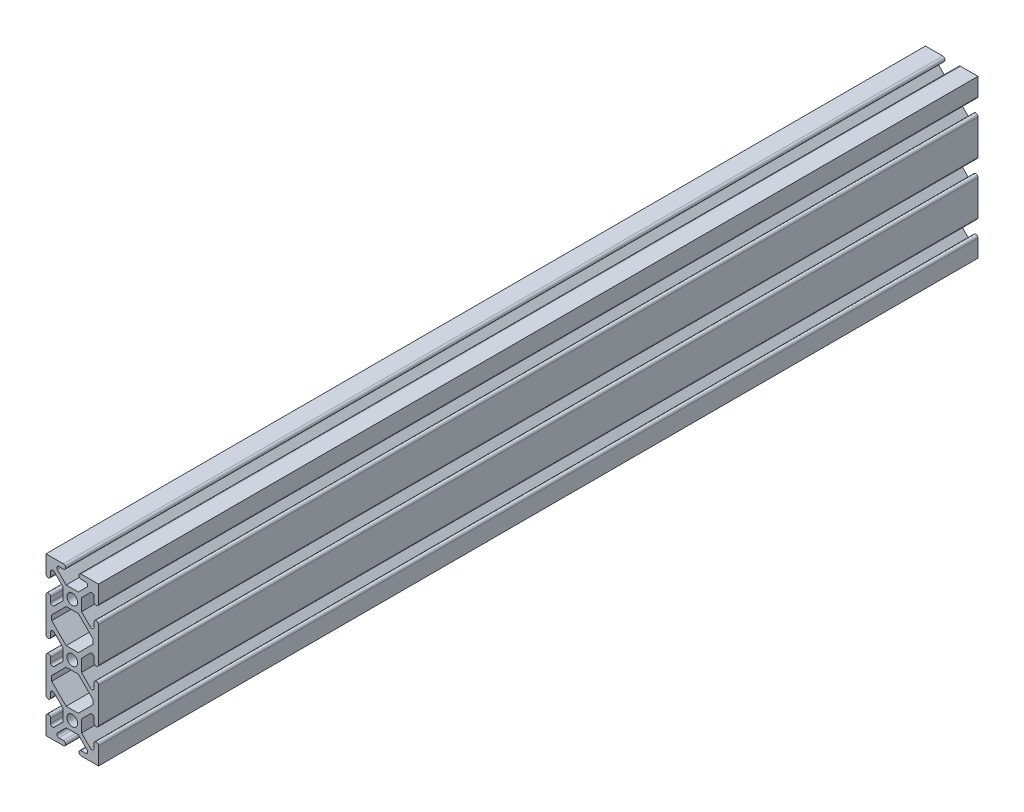
SolidWorks part; units mm, degrees
ref_plane "Front Plane" through (0, 0, 0) normal (0, 0, 1) x (1, 0, 0)
ref_plane "Top Plane" through (0, 0, 0) normal (0, 1, 0) x (1, 0, 0)
ref_plane "Right Plane" through (0, 0, 0) normal (1, 0, 0) x (0, 0, -1)
sketch "Sketch1" plane through (0, 0, 0) normal (0, 0, 1) x (1, 0, 0)
  line L0 (-8.7558, -7.1932) -> (-4.5085, -2.9459)
  line L1 (-9.9314, 13.906) -> (-9.9314, 11.494)
  line L2 (-9.9314, 13.906) -> (-2.9459, 20.8915)
  line L3 (2.9459, 4.5085) -> (9.9314, 11.494)
  line L4 (-4.5085, 2.9459) -> (-4.5085, -2.9459)
  line L5 (-4.5085, 2.9459) -> (-8.7558, 7.1932)
  line L6 (8.7558, 7.1932) -> (4.5085, 2.9459)
  line L7 (4.5085, -2.9459) -> (4.5085, 2.9459)
  line L8 (-9.9314, -11.494) -> (-9.9314, -13.906)
  line L9 (-7.1932, -34.1558) -> (-2.9459, -29.9085)
  line L10 (2.9459, -29.9085) -> (-2.9459, -29.9085)
  line L11 (-8.7558, -32.5932) -> (-4.5085, -28.3459)
  line L12 (-9.9314, -11.494) -> (-2.9459, -4.5085)
  line L13 (8.7558, -32.5932) -> (4.5085, -28.3459)
  line L14 (2.9459, -29.9085) -> (7.1932, -34.1558)
  line L15 (-4.5085, -22.4541) -> (-4.5085, -28.3459)
  line L16 (-12.7, 21.0977) -> (-12.7, 4.3023)
  line L17 (-12.7, -4.3023) -> (-12.7, -21.0977)
  line L18 (-12.7, 29.7023) -> (-12.7, 38.1)
  line L19 (-10.4902, 29.7023) -> (-10.4902, 31.8748)
  line L23 (-10.4902, 18.9252) -> (-10.4902, 21.0977)
  line L24 (-12.7, 38.1) -> (-4.3023, 38.1)
  line L25 (4.3023, 38.1) -> (12.7, 38.1)
  line L26 (12.7, 38.1) -> (12.7, 29.7023)
  line L27 (12.7, 21.0977) -> (12.7, 4.3023)
  line L28 (12.7, -4.3023) -> (12.7, -21.0977)
  line L29 (-10.4902, 4.3023) -> (-10.4902, 6.4748)
  line L33 (-10.4902, -6.4748) -> (-10.4902, -4.3023)
  line L34 (-12.7, -29.7023) -> (-12.7, -38.1)
  line L35 (-12.7, -38.1) -> (-4.3023, -38.1)
  line L36 (4.3023, -38.1) -> (12.7, -38.1)
  line L37 (12.7, -38.1) -> (12.7, -29.7023)
  line L38 (-4.5085, -22.4541) -> (-8.7558, -18.2068)
  line L39 (-10.4902, -21.0977) -> (-10.4902, -18.9252)
  line L43 (-10.4902, -31.8748) -> (-10.4902, -29.7023)
  line L44 (4.5085, -22.4541) -> (4.5085, -28.3459)
  line L45 (4.5085, -22.4541) -> (8.7558, -18.2068)
  line L46 (2.9459, -20.8915) -> (-2.9459, -20.8915)
  line L47 (-2.9459, -20.8915) -> (-9.9314, -13.906)
  line L48 (-4.3023, -35.8902) -> (-6.4748, -35.8902)
  line L52 (6.4748, -35.8902) -> (4.3023, -35.8902)
  line L53 (2.9459, -4.5085) -> (-2.9459, -4.5085)
  line L54 (2.9459, -4.5085) -> (9.9314, -11.494)
  line L55 (9.9314, -11.494) -> (9.9314, -13.906)
  line L56 (9.9314, -13.906) -> (2.9459, -20.8915)
  line L57 (10.4902, -29.7023) -> (10.4902, -31.8748)
  line L61 (10.4902, -18.9252) -> (10.4902, -21.0977)
  line L62 (4.5085, -2.9459) -> (8.6807, -7.267)
  line L63 (2.9459, 4.5085) -> (-2.9459, 4.5085)
  line L64 (-2.9459, 4.5085) -> (-9.9314, 11.494)
  line L65 (9.9314, 13.906) -> (9.9314, 11.494)
  line L66 (2.9459, 20.8915) -> (-2.9459, 20.8915)
  line L67 (10.4902, -4.3023) -> (10.4902, -6.4748)
  line L71 (10.4902, 6.4748) -> (10.4902, 4.3023)
  line L72 (2.9459, 20.8915) -> (9.9314, 13.906)
  line L73 (-8.7558, 32.5932) -> (-4.5085, 28.3459)
  line L74 (-7.1932, 34.1558) -> (-2.9459, 29.9085)
  line L75 (8.7558, 18.2068) -> (4.5085, 22.4541)
  line L76 (-4.5085, 22.4541) -> (-4.5085, 28.3459)
  line L77 (10.4902, 21.0977) -> (10.4902, 18.9252)
  line L81 (10.4902, 31.8748) -> (10.4902, 29.7023)
  line L82 (-4.5085, 22.4541) -> (-8.7558, 18.2068)
  line L83 (2.9459, 29.9085) -> (-2.9459, 29.9085)
  line L84 (2.9459, 29.9085) -> (7.1932, 34.1558)
  line L85 (4.5085, 28.3459) -> (4.5085, 22.4541)
  line L86 (4.3023, 35.8902) -> (6.4748, 35.8902)
  line L90 (-6.4748, 35.8902) -> (-4.3023, 35.8902)
  line L91 (4.5085, 28.3459) -> (8.7558, 32.5932)
  circle A0 centre (0, 25.4) radius 2.6035
  arc A5 (10.4902, -6.4748) -> (8.6807, -7.267) centre (9.4899, -6.6526) cw
  circle A17 centre (0, -25.4) radius 2.6035
  circle A18 centre (0, 0) radius 2.6035
  arc A24 (-12.7, 29.7023) -> (-10.4902, 29.7023) centre (-11.5951, 29.7023) ccw
  arc A25 (-10.4902, 31.8748) -> (-8.7558, 32.5932) centre (-9.4742, 31.8748) cw
  arc A28 (-8.7558, 18.2068) -> (-10.4902, 18.9252) centre (-9.4742, 18.9252) cw
  arc A29 (-10.4902, 21.0977) -> (-12.7, 21.0977) centre (-11.5951, 21.0977) ccw
  arc A34 (-12.7, 4.3023) -> (-10.4902, 4.3023) centre (-11.5951, 4.3023) ccw
  arc A35 (-10.4902, 6.4748) -> (-8.7558, 7.1932) centre (-9.4742, 6.4748) cw
  arc A38 (-8.7558, -7.1932) -> (-10.4902, -6.4748) centre (-9.4742, -6.4748) cw
  arc A39 (-10.4902, -4.3023) -> (-12.7, -4.3023) centre (-11.5951, -4.3023) ccw
  arc A44 (-12.7, -21.0977) -> (-10.4902, -21.0977) centre (-11.5951, -21.0977) ccw
  arc A45 (-10.4902, -18.9252) -> (-8.7558, -18.2068) centre (-9.4742, -18.9252) cw
  arc A48 (-8.7558, -32.5932) -> (-10.4902, -31.8748) centre (-9.4742, -31.8748) cw
  arc A49 (-10.4902, -29.7023) -> (-12.7, -29.7023) centre (-11.5951, -29.7023) ccw
  arc A55 (-4.3023, -38.1) -> (-4.3023, -35.8902) centre (-4.3023, -36.9951) ccw
  arc A56 (-6.4748, -35.8902) -> (-7.1932, -34.1558) centre (-6.4748, -34.8742) cw
  arc A59 (7.1932, -34.1558) -> (6.4748, -35.8902) centre (6.4748, -34.8742) cw
  arc A60 (4.3023, -35.8902) -> (4.3023, -38.1) centre (4.3023, -36.9951) ccw
  arc A66 (12.7, -29.7023) -> (10.4902, -29.7023) centre (11.5951, -29.7023) ccw
  arc A67 (10.4902, -31.8748) -> (8.7558, -32.5932) centre (9.4742, -31.8748) cw
  arc A70 (8.7558, -18.2068) -> (10.4902, -18.9252) centre (9.4742, -18.9252) cw
  arc A71 (10.4902, -21.0977) -> (12.7, -21.0977) centre (11.5951, -21.0977) ccw
  arc A76 (12.7, -4.3023) -> (10.4902, -4.3023) centre (11.5951, -4.3023) ccw
  arc A80 (8.7558, 7.1932) -> (10.4902, 6.4748) centre (9.4742, 6.4748) cw
  arc A81 (10.4902, 4.3023) -> (12.7, 4.3023) centre (11.5951, 4.3023) ccw
  arc A86 (12.7, 21.0977) -> (10.4902, 21.0977) centre (11.5951, 21.0977) ccw
  arc A87 (10.4902, 18.9252) -> (8.7558, 18.2068) centre (9.4742, 18.9252) cw
  arc A90 (8.7558, 32.5932) -> (10.4902, 31.8748) centre (9.4742, 31.8748) cw
  arc A91 (10.4902, 29.7023) -> (12.7, 29.7023) centre (11.5951, 29.7023) ccw
  arc A97 (4.3023, 38.1) -> (4.3023, 35.8902) centre (4.3023, 36.9951) ccw
  arc A98 (6.4748, 35.8902) -> (7.1932, 34.1558) centre (6.4748, 34.8742) cw
  arc A101 (-7.1932, 34.1558) -> (-6.4748, 35.8902) centre (-6.4748, 34.8742) cw
  arc A102 (-4.3023, 35.8902) -> (-4.3023, 38.1) centre (-4.3023, 36.9951) ccw
  point P6 (-9.9314, 12.7)
  point P10 (9.9314, 12.7)
  point P12 (0, 20.8915)
  point P18 (-4.5085, 0)
  point P21 (4.5085, 0)
  point P25 (0, 4.5085)
  point P28 (-4.5085, 0)
  point P29 (4.5085, 0)
  point P34 (0, -29.9085)
  point P39 (-9.9314, -12.7)
  point P40 (-4.5085, -25.4)
  point P42 (4.5085, -25.4)
  point P44 (0, -20.8915)
  point P47 (0, -4.5085)
  point P54 (0, -20.8915)
  point P59 (-9.9314, -12.7)
  point P60 (9.9314, -12.7)
  point P61 (-4.5085, -25.4)
  point P62 (4.5085, -25.4)
  point P63 (0, -29.9085)
  point P64 (0, -4.5085)
  point P65 (0, 4.5085)
  point P66 (-9.9314, 12.7)
  point P73 (-4.5085, 25.4)
  point P75 (0, 29.9085)
  point P77 (4.5085, 25.4)
  point P85 (0, 20.8915)
  point P86 (9.9314, 12.7)
  point P87 (-4.5085, 25.4)
  point P88 (4.5085, 25.4)
  point P89 (0, 29.9085)
extrude "Boss-Extrude1" add sketch "Sketch1" against normal blind 425.45
